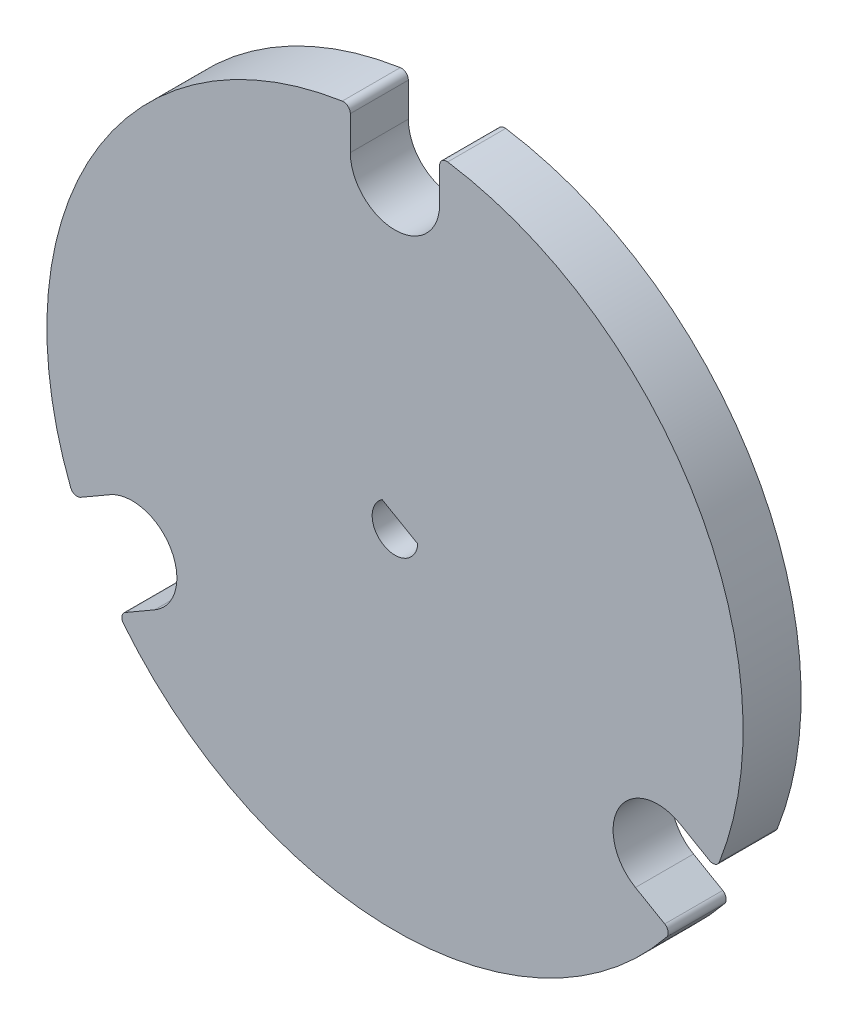
SolidWorks part; units mm, degrees
material "Acrylic (Medium-high impact)"
ref_plane "Front Plane" through (0, 0, 0) normal (0, 0, 1) x (1, 0, 0)
ref_plane "Top Plane" through (0, 0, 0) normal (0, 1, 0) x (1, 0, 0)
ref_plane "Right Plane" through (0, 0, 0) normal (1, 0, 0) x (0, 0, -1)
sketch "Sketch1" plane through (0, 0, 0) normal (0, 0, 1) x (1, 0, 0)
  circle A0 centre (0, 0) radius 38.1
  dimension "D1" = 76.2
extrude "Boss-Extrude1" add sketch "Sketch1" along normal blind 6.35
sketch "Sketch2" plane through (0, 0, 6.35) normal (0, 0, 1) x (1, 0, 0)
  line L0 (-4.8895, 33.2105) -> (-4.8895, 37.785)
  line L1 (0, 33.2105) -> (-28.7611, -16.6052) construction
  line L2 (-28.7611, -16.6052) -> (28.7611, -16.6052) construction
  line L3 (28.7611, -16.6052) -> (0, 33.2105) construction
  line L4 (4.8895, 33.2105) -> (4.8895, 37.785)
  line L5 (31.2059, -12.3708) -> (35.1675, -14.658)
  line L6 (26.3164, -20.8397) -> (30.278, -23.1269)
  line L7 (-26.3164, -20.8397) -> (-30.278, -23.1269)
  line L8 (-31.2059, -12.3708) -> (-35.1675, -14.658)
  circle A0 centre (0, 0) radius 16.6052 construction
  arc A1 (-4.8895, 33.2105) -> (4.8895, 33.2105) centre (0, 33.2105) ccw
  circle A2 centre (0, 0) radius 38.1 construction
  arc A3 (-4.8895, 37.785) -> (4.8895, 37.785) centre (0, 0) cw
  arc A4 (31.2059, -12.3708) -> (26.3164, -20.8397) centre (28.7611, -16.6052) ccw
  arc A5 (35.1675, -14.658) -> (30.278, -23.1269) centre (0, 0) cw
  arc A6 (-26.3164, -20.8397) -> (-31.2059, -12.3708) centre (-28.7611, -16.6053) ccw
  arc A7 (-30.278, -23.1269) -> (-35.1675, -14.658) centre (0, 0) cw
  point P25 (0, 0)
  dimension "D1" = 9.779
  dimension "D2" = 3
extrude "Cut-Extrude1" cut sketch "Sketch2" against normal through all
sketch "Sketch3" plane through (0, 0, 6.35) normal (0, 0, 1) x (1, 0, 0)
  line L2 (2.4934, -0.1813) -> (-1.4037, 2.0687)
  arc A1 (-1.4037, 2.0687) -> (2.4934, -0.1813) centre (0, 0) ccw
extrude "Cut-Extrude2" cut sketch "Sketch3" against normal through all
fillet "Fillet1" radius 0.762 6 edges at (-4.8895, 37.785, 3.175) (4.8895, 37.785, 3.175) (-30.278, -23.1269, 3.175) (-35.1675, -14.658, 3.175) (30.278, -23.1269, 3.175) (35.1675, -14.658, 3.175)
